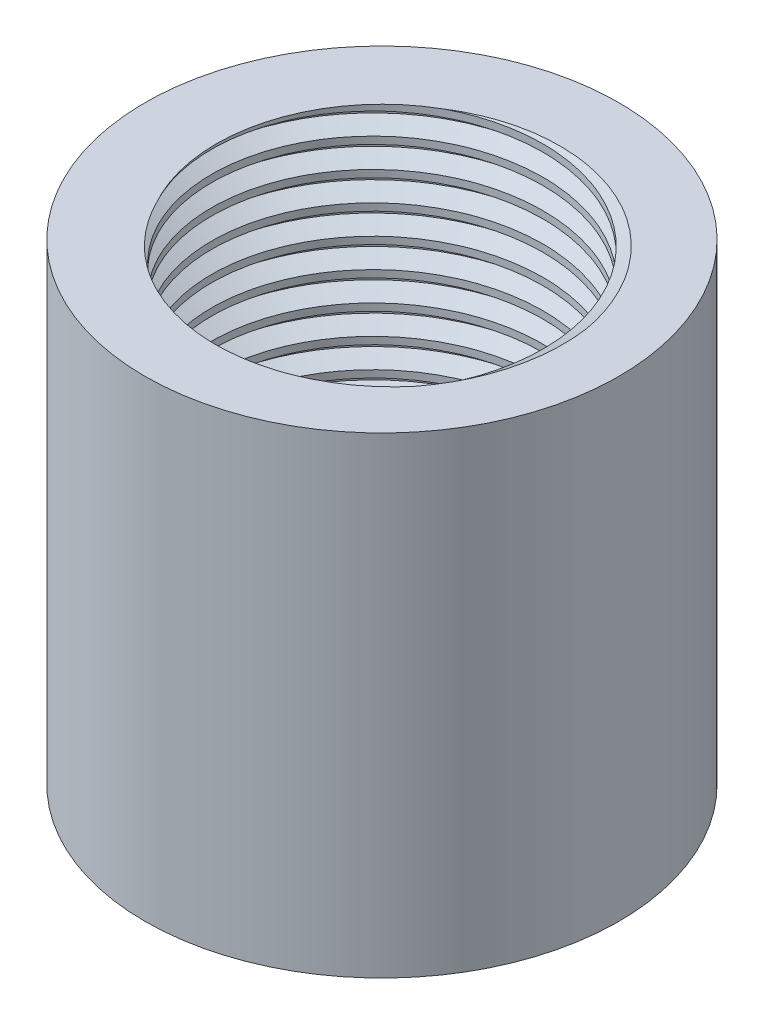
SolidWorks part; units mm, degrees
ref_plane "Front Plane" through (0, 0, 0) normal (0, 0, 1) x (1, 0, 0)
ref_plane "Top Plane" through (0, 0, 0) normal (0, 1, 0) x (1, 0, 0)
ref_plane "Right Plane" through (0, 0, 0) normal (1, 0, 0) x (0, 0, -1)
sketch "Sketch1" plane through (0, 0, 0) normal (0, 1, 0) x (1, 0, 0)
  circle A0 centre (0, 0) radius 8.6
  circle A1 centre (0, 0) radius 12.3
  dimension "D1" = 24.6
  dimension "D2" = 3.7
extrude "Boss-Extrude1" add sketch "Sketch1" along normal blind 20
sketch "Sketch3" plane through (0, 0, 0) normal (0, 1, 0) x (1, 0, 0)
  circle A0 centre (0, 0) radius 12.3 construction
  circle A1 centre (0, 0) radius 12.3
extrude "Boss-Extrude2" add sketch "Sketch3" against normal blind 4.5
sketch "Sketch4" plane through (0, -4.5, 0) normal (0, -1, 0) x (1, 0, 0)
  circle A0 centre (0, 0) radius 4.25
  dimension "D1" = 8.5
extrude "Cut-Extrude1" cut sketch "Sketch4" against normal through all
sketch "Sketch5" plane through (0, -4.5, 0) normal (0, -1, 0) x (1, 0, 0)
  circle A0 centre (0, 0) radius 6.85
  dimension "D1" = 13.7
extrude "Cut-Extrude2" cut sketch "Sketch5" against normal blind 1
thread "Thread1" pitch 1.5 method cut profile "Thread Profile1" start angle 0, offset 0, length 0, pitch 1.5, diameter 17.2
ref_plane "Plane1" through (8.6, 0, 0) normal (0, 0, 1) x (1, 0, 0)
sketch "Thread Profile1" plane through (8.6, 0, 0) normal (0, 0, 1) x (1, 0, 0)
  line L0 (0, 0) -> (0, 1.5) construction
  line L1 (0, 0) -> (0.8119, 0.4687)
  line L2 (0.8119, 0.4687) -> (0.8119, 0.6562)
  line L3 (0.8119, 0.6562) -> (0, 1.125)
  line L4 (0.8119, 0.5625) -> (0, 0.5625) construction
  line L11 (0, 0) -> (0, 1.125)
  point P2 (0, 0)
  dimension "Pitch" = 1.5
  dimension "Profile_Angle" = 60
  dimension "Profile_Land" = 0.1875
  dimension "Profile_Height" = 0.8119
